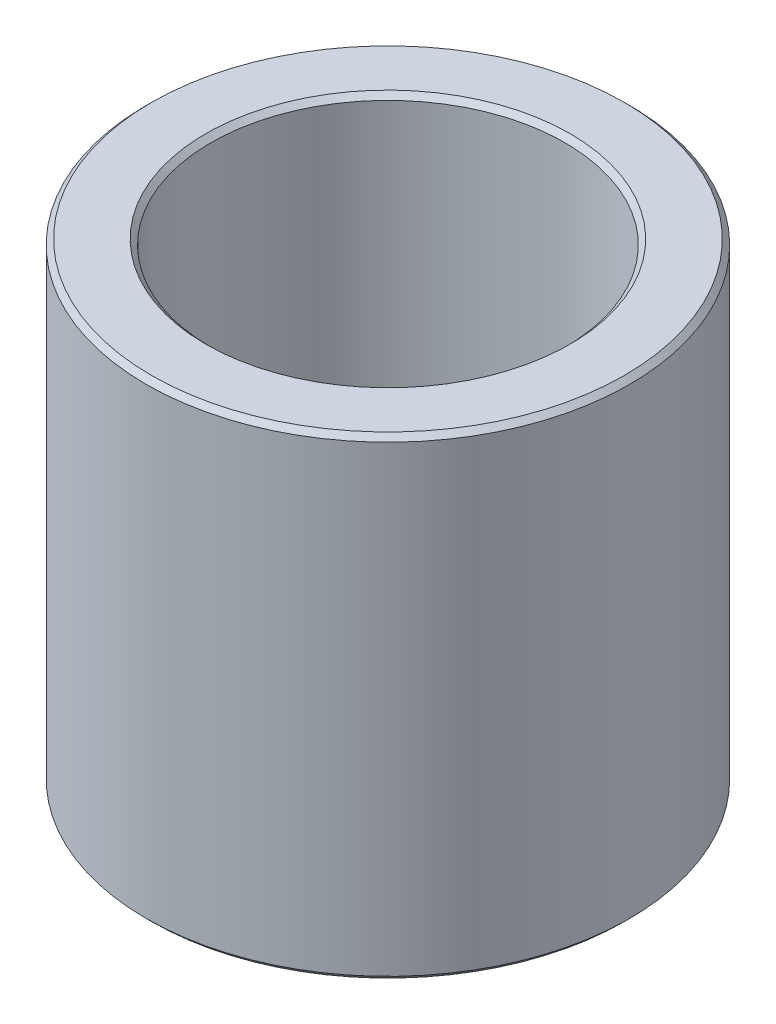
SolidWorks part; units mm, degrees
ref_plane "Front Plane" through (0, 0, 0) normal (0, 0, 1) x (1, 0, 0)
ref_plane "Top Plane" through (0, 0, 0) normal (0, 1, 0) x (1, 0, 0)
ref_plane "Right Plane" through (0, 0, 0) normal (1, 0, 0) x (0, 0, -1)
sketch "Sketch1" plane through (0, 0, 0) normal (0, 1, 0) x (1, 0, 0)
  circle A0 centre (0, 0) radius 32.5
  dimension "SLEEVE_OD" = 65
extrude "Boss-Extrude1" add sketch "Sketch1" along normal blind 63.6074
sketch "Sketch2" plane through (0, 0, 0) normal (0, 1, 0) x (1, 0, 0)
  circle A0 centre (0, 0) radius 23.8154
  dimension "BORE_D" = 47.6308
extrude "Cut-Extrude1" cut sketch "Sketch2" along normal through all
chamfer "Chamfer1" distance 0.6989 angle 45.086 4 edges at (0, 63.6074, 23.8154) (0, 0, 23.8154) (0, 0, 32.5) (0, 63.6074, 32.5) first distance on face at (0, 63.6074, 23.8154) first distance on face at (0, 0, 23.8154) first distance on face at (0, 63.6074, 32.5)
